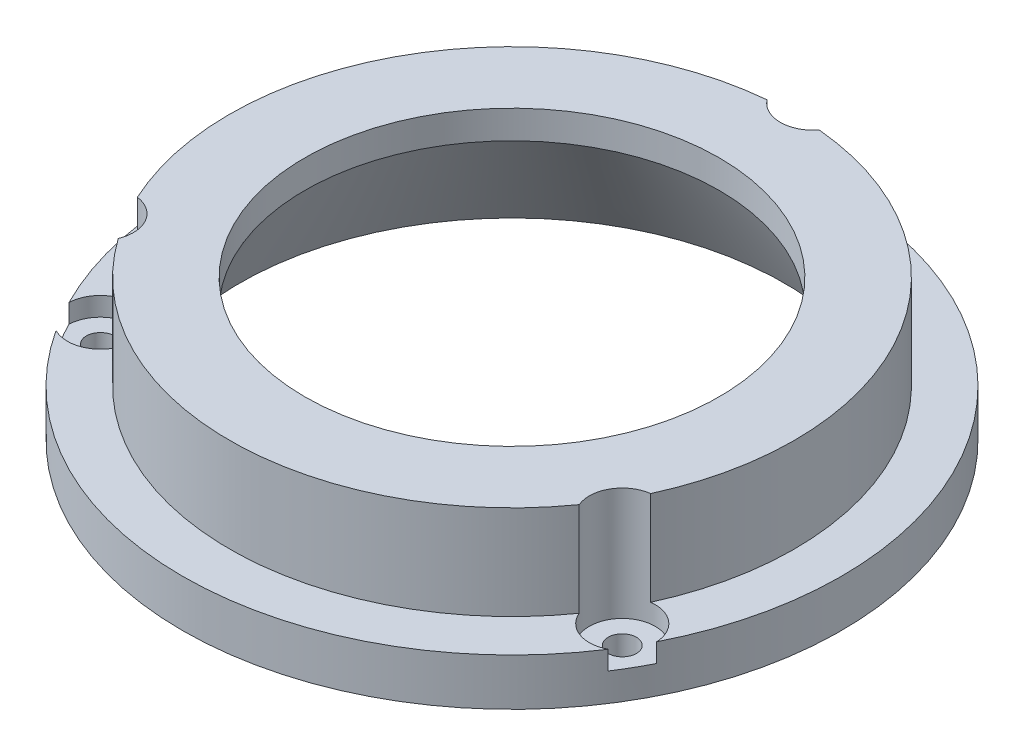
SolidWorks part; units mm, degrees
ref_plane "Front Plane" through (0, 0, 0) normal (0, 0, 1) x (1, 0, 0)
ref_plane "Top Plane" through (0, 0, 0) normal (0, 1, 0) x (1, 0, 0)
ref_plane "Right Plane" through (0, 0, 0) normal (1, 0, 0) x (0, 0, -1)
sketch "Sketch1" plane through (0, 0, 0) normal (0, 1, 0) x (1, 0, 0)
  circle A0 centre (0, 0) radius 30
  circle A1 centre (0, 0) radius 22
  dimension "D1" = 60
  dimension "D2" = 8
extrude "Boss-Extrude1" add sketch "Sketch1" along normal blind 10
sketch "Sketch2" plane through (0, 0, 0) normal (0, 1, 0) x (1, 0, 0)
  circle A0 centre (0, 0) radius 35
  circle A1 centre (0, 0) radius 22
  circle A2 centre (0, 0) radius 22 construction
  dimension "D1" = 70
extrude "Boss-Extrude2" add sketch "Sketch2" against normal blind 5
sketch "Sketch3" plane through (0, 0, 0) normal (0, 1, 0) x (1, 0, 0)
  circle A0 centre (0, 32) radius 1.5
  point P2 (0, 0)
  dimension "D2" = 3
  dimension "D1" = 32
extrude "Cut-Extrude1" cut sketch "Sketch3" against normal through all
sketch "Sketch4" plane through (0, 0, 0) normal (0, 1, 0) x (1, 0, 0)
  circle A0 centre (0, 32) radius 3.5
  dimension "D1" = 7
extrude "Cut-Extrude2" cut sketch "Sketch4" against normal blind 2 and the other way through all
pattern_circular "CirPattern1" count 3 over 360 about axis through (0, -5, 0) along (0, 1, 0) of "Cut-Extrude1", "Cut-Extrude2"
chamfer "Chamfer1" distance 12 angle 30 1 edges at (0, -5, 22) first distance on face at (0, 10, 22)
